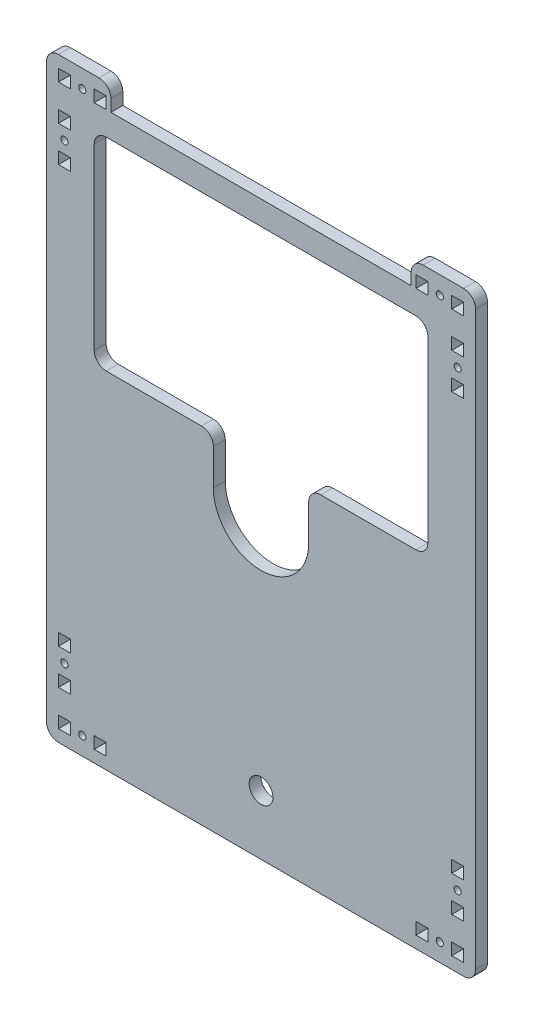
SolidWorks part; units mm, degrees
ref_plane "Front Plane" through (0, 0, 0) normal (0, 0, 1) x (1, 0, 0)
ref_plane "Top Plane" through (0, 0, 0) normal (0, 1, 0) x (1, 0, 0)
ref_plane "Right Plane" through (0, 0, 0) normal (1, 0, 0) x (0, 0, -1)
sketch "Sketch1" plane through (0, 0, 0) normal (0, 0, 1) x (1, 0, 0)
  line L0 (0, 0) -> (187.0096, 0) construction
  line L1 (-90, 125) -> (90, 125) construction
  line L2 (-90, 125) -> (-90, -125)
  line L3 (-90, -125) -> (90, -125)
  line L4 (90, 125) -> (90, -125)
  line L5 (0, 0) -> (0, 134.5508) construction
  line L6 (-90, 117.5) -> (90, 117.5) construction
  line L7 (-70, 105) -> (70, 105)
  line L8 (70, 105) -> (70, 0) construction
  line L9 (70, 0) -> (-70, 0) construction
  line L10 (-70, 0) -> (-70, 105) construction
  line L11 (-70, 0) -> (-20, 0) construction
  line L12 (20, 0) -> (70, 0) construction
  line L13 (82.5, 125) -> (82.5, -125) construction
  line L14 (0, 0) -> (0, -125) construction
  line L15 (-90, 125) -> (-63, 125)
  line L16 (-63, 125) -> (-63, 115)
  line L17 (-63, 115) -> (63, 115)
  line L18 (63, 115) -> (63, 125)
  line L19 (63, 125) -> (90, 125)
  line L20 (-20, 0) -> (-20, 20)
  line L21 (-20, 20) -> (-70, 20)
  line L22 (-70, 20) -> (-70, 105)
  line L23 (70, 20) -> (70, 105)
  line L24 (20, 20) -> (70, 20)
  line L25 (20, 0) -> (20, 20)
  arc A0 (-20, 0) -> (20, 0) centre (0, 0) ccw
  circle A1 centre (0, -100) radius 5
  line B0 (-80, 117.5) -> (-70, 117.5) construction
  line B1 (-80, 120) -> (-85, 120)
  line B2 (-80, 120) -> (-80, 115)
  line B3 (-80, 115) -> (-85, 115)
  line B4 (-85, 120) -> (-85, 115)
  line B5 (-70, 120) -> (-65, 120)
  line B6 (-70, 120) -> (-70, 115)
  line B7 (-70, 115) -> (-65, 115)
  line B8 (-65, 120) -> (-65, 115)
  line B9 (-75, 117.5) -> (-75, 124.4724) construction
  circle B10 centre (-75, 117.5) radius 1.5
  line B11 (-80, -120) -> (-85, -120)
  line B12 (-80, -120) -> (-80, -115)
  line B13 (-80, -115) -> (-85, -115)
  line B14 (-85, -120) -> (-85, -115)
  line B15 (-70, -120) -> (-65, -120)
  line B16 (-70, -120) -> (-70, -115)
  line B17 (-70, -115) -> (-65, -115)
  line B18 (-65, -120) -> (-65, -115)
  circle B19 centre (-75, -117.5) radius 1.5
  line B20 (80, -120) -> (85, -120)
  line B21 (80, -120) -> (80, -115)
  line B22 (80, -115) -> (85, -115)
  line B23 (85, -120) -> (85, -115)
  line B24 (70, -120) -> (65, -120)
  line B25 (70, -120) -> (70, -115)
  line B26 (70, -115) -> (65, -115)
  line B27 (65, -120) -> (65, -115)
  circle B28 centre (75, -117.5) radius 1.5
  line B29 (80, 120) -> (85, 120)
  line B30 (80, 120) -> (80, 115)
  line B31 (80, 115) -> (85, 115)
  line B32 (85, 120) -> (85, 115)
  line B33 (70, 120) -> (65, 120)
  line B34 (70, 120) -> (70, 115)
  line B35 (70, 115) -> (65, 115)
  line B36 (65, 120) -> (65, 115)
  line B37 (75, 117.5) -> (75, 124.4724) construction
  circle B38 centre (75, 117.5) radius 1.5
  line B39 (82.5, 100) -> (82.5, 90) construction
  line B40 (80, 100) -> (80, 105)
  line B41 (80, 100) -> (85, 100)
  line B42 (85, 100) -> (85, 105)
  line B43 (80, 105) -> (85, 105)
  line B44 (80, 90) -> (80, 85)
  line B45 (80, 90) -> (85, 90)
  line B46 (85, 90) -> (85, 85)
  line B47 (80, 85) -> (85, 85)
  line B48 (82.5, 95) -> (75.5276, 95) construction
  circle B49 centre (82.5, 95) radius 1.5
  line B50 (80, -100) -> (80, -105)
  line B51 (80, -100) -> (85, -100)
  line B52 (85, -100) -> (85, -105)
  line B53 (80, -105) -> (85, -105)
  line B54 (80, -90) -> (80, -85)
  line B55 (80, -90) -> (85, -90)
  line B56 (85, -90) -> (85, -85)
  line B57 (80, -85) -> (85, -85)
  circle B58 centre (82.5, -95) radius 1.5
  line B59 (-80, 100) -> (-80, 105)
  line B60 (-80, 100) -> (-85, 100)
  line B61 (-85, 100) -> (-85, 105)
  line B62 (-80, 105) -> (-85, 105)
  line B63 (-80, 90) -> (-80, 85)
  line B64 (-80, 90) -> (-85, 90)
  line B65 (-85, 90) -> (-85, 85)
  line B66 (-80, 85) -> (-85, 85)
  circle B67 centre (-82.5, 95) radius 1.5
  line B68 (-80, -100) -> (-80, -105)
  line B69 (-80, -100) -> (-85, -100)
  line B70 (-85, -100) -> (-85, -105)
  line B71 (-80, -105) -> (-85, -105)
  line B72 (-80, -90) -> (-80, -85)
  line B73 (-80, -90) -> (-85, -90)
  line B74 (-85, -90) -> (-85, -85)
  line B75 (-80, -85) -> (-85, -85)
  circle B76 centre (-82.5, -95) radius 1.5
  dimension "D1" = 150
  dimension "D8" = 20
  dimension "D10" = 10
  dimension "D2" = 7.5
  dimension "D3" = 250
  dimension "D4" = 180
  dimension "D5" = 10
  dimension "D6" = 20
  dimension "D7" = 20
  dimension "D9" = 30
  dimension "D11" = 25
  dimension "D12" = 7.5
  dimension "D13" = 2
sketch_block_instance "Trou M3 plots 5mm-2"
sketch_block "Trou M3 plots 5mm" parameters "D2"=3, "D1"=5, "D3"=5, "D4"=10
sketch_block_instance "Trou M3 plots 5mm-4"
sketch_block_instance "Trou M3 plots 5mm-5"
sketch_block_instance "Trou M3 plots 5mm-6"
sketch_block_instance "Trou M3 plots 5mm-7"
sketch_block_instance "Trou M3 plots 5mm-8"
sketch_block_instance "Trou M3 plots 5mm-9"
sketch_block_instance "Trou M3 plots 5mm-10"
extrude "Boss-Extrude1" add sketch "Sketch1" along normal blind 5
fillet "Fillet1" radius 5 12 edges at (-90, -125, 2.5) (90, -125, 2.5) (-90, 125, 2.5) (-63, 125, 2.5) (63, 125, 2.5) (90, 125, 2.5) (-70, 105, 2.5) (70, 105, 2.5) (70, 20, 2.5) (20, 20, 2.5) (-20, 20, 2.5) (-70, 20, 2.5)
